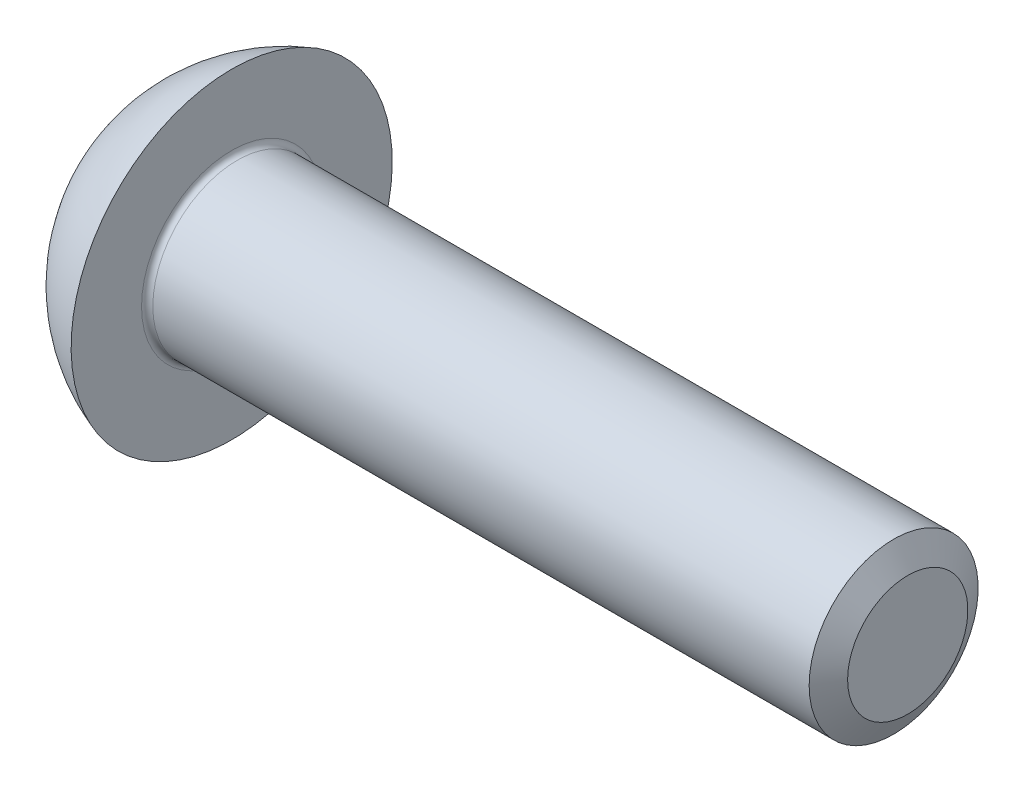
SolidWorks part; units mm, degrees
ref_plane "前视基准面" through (0, 0, 0) normal (0, 0, 1) x (1, 0, 0)
ref_plane "上视基准面" through (0, 0, 0) normal (0, 1, 0) x (1, 0, 0)
ref_plane "右视基准面" through (0, 0, 0) normal (1, 0, 0) x (0, 0, -1)
sketch "草图1" plane through (0, 0, 0) normal (0, 0, 1) x (1, 0, 0)
  line L0 (-13.65, 0) -> (0, 0) construction
  line L1 (0, 1.5) -> (-11.9, 1.5)
  line L2 (-12, 1.6) -> (-12, 2.85)
  line L3 (-13.65, 0) -> (-13.65, 1.5)
  line L4 (0, 1.5) -> (0, 0)
  line L5 (-13.65, 0) -> (0, 0)
  arc A0 (-12, 2.85) -> (-13.65, 1.5) centre (-11.0455, 0) ccw
  arc A1 (-11.9, 1.5) -> (-12, 1.6) centre (-11.9, 1.6) cw
  point P10 (-12, 1.5)
  dimension "r" = 0.1
  dimension "d" = 3
  dimension "dk" = 5.7
  dimension "k" = 1.65
  dimension "l" = 12
revolve "旋转1" add sketch "草图1" angle 360 about L0
cosmetic thread "装饰螺纹线1" parameters "D1"=2, "D2"=2.58
sketch "草图2" plane through (-13.65, 0, 0) normal (-1, 0, 0) x (0, 0, 1)
  line L1 (0, 1.1547) -> (-1, 0.5774)
  line L2 (-1, 0.5774) -> (-1, -0.5774)
  line L3 (-1, -0.5774) -> (0, -1.1547)
  line L4 (0, -1.1547) -> (1, -0.5774)
  line L5 (1, -0.5774) -> (1, 0.5774)
  line L6 (1, 0.5774) -> (0, 1.1547)
  circle A0 centre (0, 0) radius 1 construction
  dimension "s" = 2
extrude "切除-拉伸1" cut sketch "草图2" against normal blind 1.65
sketch "草图6" plane through (0, 0, 0) normal (0, 0, 1) x (1, 0, 0)
  line L0 (-12.61, 1.1547) -> (-12, 0)
  line L1 (-11.7, 1.1547) -> (-11.7, 0)
  line L2 (-11.7, 1.1547) -> (-12.61, 1.1547)
  line L3 (-13.65, 0) -> (-12, 0) construction
  line L4 (-11.7, 0) -> (-12, 0)
  line L5 (-13.65, 0) -> (-15.95, 0) construction
  dimension "t" = 1.04
  dimension "e-s" = 0.3
  dimension "k" = 1.65
  dimension "e" = 2.3
revolve "旋转2" add sketch "草图6" angle 360 about L3
sketch "草图7" plane through (0, 0, 0) normal (0, 0, 1) x (1, 0, 0)
  line L3 (-13.65, 1.1547) -> (-13.35, 0)
  line L4 (-13.65, 0) -> (-13.35, 0) construction
  line L7 (-13.65, 1.1547) -> (-13.65, 0)
  line L8 (-13.65, 0) -> (-13.35, 0)
  dimension "e-s" = 0.3
revolve "切除-旋转5" cut sketch "草图7" angle 360 about L4
sketch "草图4" plane through (0, 0, 0) normal (0, 0, 1) x (1, 0, 0)
  line L0 (-0.25, 1.5) -> (0, 1.067)
  line L1 (-0.25, 1.5) -> (0.25, 1.5)
  line L2 (0.25, 1.5) -> (0, 1.067)
  line L4 (0, -1.5) -> (0, 1.5) construction
  line L5 (-0.25, 0) -> (0.25, 0) construction
  dimension "d" = 1.5
  dimension "p" = 0.5
revolve "切除-旋转1" cut sketch "草图4" angle 360 about L5
ref_axis "基准轴1" through (-8.1887, 0, 0) along (1, 0, 0)
pattern_linear "阵列(线性)1" [suppressed] count 4 spacing 0.5 along (-1, 0, 0) of bodies 104
equation "\"D2@装饰螺纹线1\" = \"d@草图1\" * 0.86"
equation "\"k@草图6\" = \"k@切除-拉伸1\""
equation "\"e-s@草图6\" = \"e@草图6\" - \"s@草图2\""
equation "\"e-s@草图7\" = \"e-s@草图6\""
equation "\"d@草图4\" = \"d@草图1\" / 2"
equation "\"k@切除-拉伸1\" = \"k@草图1\""
equation "\"D1@阵列(线性)1\" = \"D1@装饰螺纹线1\" / \"p@草图4\""
equation "\"D3@阵列(线性)1\" = \"p@草图4\""
